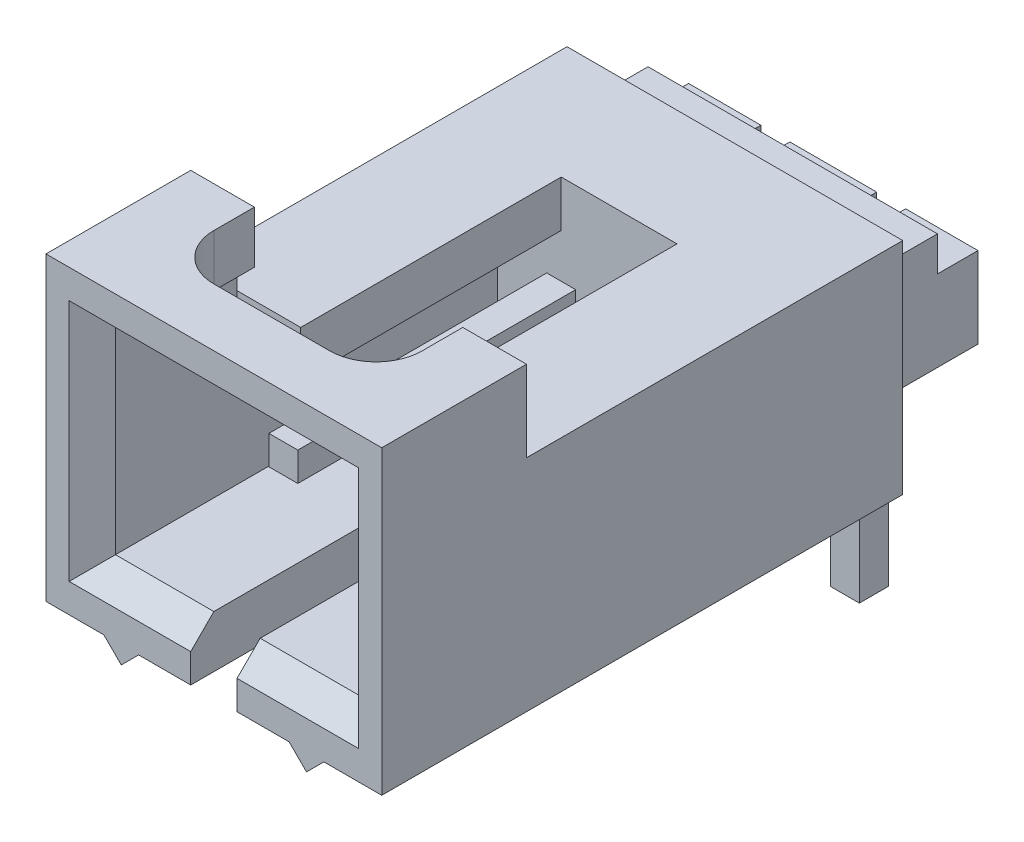
SolidWorks part; units mm, degrees
material "ABS"
ref_plane "Front Plane" through (0, 0, 0) normal (0, 0, 1) x (1, 0, 0)
ref_plane "Top Plane" through (0, 0, 0) normal (0, 1, 0) x (1, 0, 0)
ref_plane "Right Plane" through (0, 0, 0) normal (1, 0, 0) x (0, 0, -1)
ref_plane "Plane1" through (0, 0, 2.54) normal (0, 0, 1) x (1, 0, 0)
sketch "Sketch1" plane through (0, 0, 2.54) normal (0, 0, 1) x (1, 0, 0)
  line L0 (3.683, 2.286) -> (-3.683, 2.286)
  line L1 (-3.683, 2.286) -> (-3.683, -2.54)
  line L2 (-3.683, -2.54) -> (-2.413, -2.54)
  line L3 (-2.413, -2.54) -> (-1.651, -3.302)
  line L4 (-1.651, -3.302) -> (-1.651, -2.54)
  line L5 (-1.651, -2.54) -> (1.651, -2.54)
  line L6 (1.651, -2.54) -> (1.651, -3.302)
  line L7 (1.651, -3.302) -> (2.413, -2.54)
  line L8 (2.413, -2.54) -> (3.683, -2.54)
  line L9 (3.683, -2.54) -> (3.683, 2.286)
extrude "Boss-Extrude1" add sketch "Sketch1" against normal blind 8.255
sketch "Sketch2" plane through (0, 0, 2.54) normal (0, 0, 1) x (1, 0, 0)
  line L0 (2.667, -1.397) -> (2.667, 1.27)
  line L1 (2.667, 1.27) -> (1.27, 1.27)
  line L2 (1.27, 1.27) -> (1.27, 2.286)
  line L3 (1.27, 2.286) -> (-1.27, 2.286)
  line L4 (-1.27, 2.286) -> (-1.27, 1.27)
  line L5 (-1.27, 1.27) -> (-2.667, 1.27)
  line L6 (-2.667, 1.27) -> (-2.667, -1.397)
  line L7 (-2.667, -1.397) -> (-0.508, -1.397)
  line L8 (-0.508, -1.397) -> (-0.508, -2.54)
  line L9 (-0.508, -2.54) -> (0.508, -2.54)
  line L10 (0.508, -2.54) -> (0.508, -1.397)
  line L11 (0.508, -1.397) -> (2.667, -1.397)
extrude "Cut-Extrude1" cut sketch "Sketch2" against normal blind 5.715
sketch "Sketch3" plane through (0, 0, 2.54) normal (0, 0, 1) x (1, 0, 0)
  line L0 (0.508, -1.397) -> (2.667, -1.397)
  line L1 (2.667, -1.397) -> (2.667, 2.921)
  line L2 (2.667, 2.921) -> (-2.667, 2.921)
  line L3 (-2.667, 2.921) -> (-2.667, -1.397)
  line L4 (-2.667, -1.397) -> (-0.508, -1.397)
  line L5 (-0.508, -1.397) -> (-0.508, -2.54)
  line L6 (-0.508, -2.54) -> (-1.651, -2.54)
  line L7 (-1.651, -2.54) -> (-1.651, -3.302)
  line L8 (-1.651, -3.302) -> (-2.413, -2.54)
  line L9 (-2.413, -2.54) -> (-3.683, -2.54)
  line L10 (-3.683, -2.54) -> (-3.683, 4.064)
  line L11 (-3.683, 4.064) -> (3.683, 4.064)
  line L12 (3.683, 4.064) -> (3.683, -2.54)
  line L13 (3.683, -2.54) -> (2.413, -2.54)
  line L14 (2.413, -2.54) -> (1.651, -3.302)
  line L15 (1.651, -3.302) -> (1.651, -2.54)
  line L16 (1.651, -2.54) -> (0.508, -2.54)
  line L17 (0.508, -2.54) -> (0.508, -1.397)
extrude "Boss-Extrude2" add sketch "Sketch3" along normal blind 3.175
sketch "Sketch4" plane through (0, 0, 2.54) normal (0, 0, -1) x (-1, 0, 0)
  line L0 (2.286, 4.064) -> (-2.286, 4.064)
  line L1 (-2.286, 4.064) -> (-2.286, 2.921)
  line L2 (-2.286, 2.921) -> (2.286, 2.921)
  line L3 (2.286, 2.921) -> (2.286, 4.064)
extrude "Cut-Extrude2" cut sketch "Sketch4" against normal blind 1.905
sketch "Sketch5" plane through (0, 0, -3.175) normal (0, 0, 1) x (1, 0, 0)
  line L0 (-0.9525, -0.3302) -> (-1.5875, -0.3302)
  line L1 (-1.5875, -0.3302) -> (-1.5875, 0.3048)
  line L2 (-1.5875, 0.3048) -> (-0.9525, 0.3048)
  line L3 (-0.9525, 0.3048) -> (-0.9525, -0.3302)
extrude "Boss-Extrude3" add sketch "Sketch5" along normal blind 6.096
sketch "Sketch6" plane through (0, 0, -3.175) normal (0, 0, 1) x (1, 0, 0)
  line L0 (1.5875, -0.3302) -> (0.9525, -0.3302)
  line L1 (0.9525, -0.3302) -> (0.9525, 0.3048)
  line L2 (0.9525, 0.3048) -> (1.5875, 0.3048)
  line L3 (1.5875, 0.3048) -> (1.5875, -0.3302)
extrude "Boss-Extrude4" add sketch "Sketch6" along normal blind 6.096
sketch "Sketch7" plane through (0, 0, -5.715) normal (0, 0, -1) x (-1, 0, 0)
  line L0 (0.9525, -1.016) -> (0.9525, 0.0508)
  line L1 (0.9525, 0.0508) -> (1.5875, 0.0508)
  line L2 (1.5875, 0.0508) -> (1.5875, -1.016)
  line L3 (1.5875, -1.016) -> (0.9525, -1.016)
extrude "Boss-Extrude5" add sketch "Sketch7" along normal blind 1.778
sketch "Sketch8" plane through (0, 0, -5.715) normal (0, 0, -1) x (-1, 0, 0)
  line L0 (-1.5875, -1.016) -> (-1.5875, 0.0508)
  line L1 (-1.5875, 0.0508) -> (-0.9525, 0.0508)
  line L2 (-0.9525, 0.0508) -> (-0.9525, -1.016)
  line L3 (-0.9525, -1.016) -> (-1.5875, -1.016)
extrude "Boss-Extrude6" add sketch "Sketch8" along normal blind 1.778
sketch "Sketch9" plane through (0, -1.016, 0) normal (0, -1, 0) x (1, 0, 0)
  line L0 (-0.9525, -7.493) -> (-1.5875, -7.493)
  line L1 (-1.5875, -7.493) -> (-1.5875, -6.858)
  line L2 (-1.5875, -6.858) -> (-0.9525, -6.858)
  line L3 (-0.9525, -6.858) -> (-0.9525, -7.493)
extrude "Boss-Extrude7" add sketch "Sketch9" along normal blind 5.207
sketch "Sketch10" plane through (0, -1.016, 0) normal (0, -1, 0) x (1, 0, 0)
  line L0 (1.5875, -7.493) -> (0.9525, -7.493)
  line L1 (0.9525, -7.493) -> (0.9525, -6.858)
  line L2 (0.9525, -6.858) -> (1.5875, -6.858)
  line L3 (1.5875, -6.858) -> (1.5875, -7.493)
extrude "Boss-Extrude8" add sketch "Sketch10" along normal blind 5.207
ref_plane "Plane2" through (0, 0, -6.985) normal (0, 0, -1) x (-1, 0, 0)
sketch "Sketch11" plane through (0, 0, -6.985) normal (0, 0, -1) x (-1, 0, 0)
  line L0 (0.9525, 0.0508) -> (1.5875, 0.0508)
  line L1 (1.5875, 0.0508) -> (1.5875, -1.016)
  line L2 (1.5875, -1.016) -> (3.175, -1.016)
  line L3 (3.175, -1.016) -> (3.175, 1.524)
  line L4 (3.175, 1.524) -> (-3.175, 1.524)
  line L5 (-3.175, 1.524) -> (-3.175, -1.016)
  line L6 (-3.175, -1.016) -> (-1.5875, -1.016)
  line L7 (-1.5875, -1.016) -> (-1.5875, 0.0508)
  line L8 (-1.5875, 0.0508) -> (-0.9525, 0.0508)
  line L9 (-0.9525, 0.0508) -> (-0.9525, -1.016)
  line L10 (-0.9525, -1.016) -> (0.9525, -1.016)
  line L11 (0.9525, -1.016) -> (0.9525, 0.0508)
extrude "Boss-Extrude9" add sketch "Sketch11" against normal up to surface (1.27 mm away) up to face at (-1.27, -0.4826, -5.715)
ref_plane "Plane3" through (0, 0, -7.874) normal (0, 0, -1) x (-1, 0, 0)
sketch "Sketch12" plane through (0, 0, -7.874) normal (0, 0, -1) x (-1, 0, 0)
  line L0 (1.5875, -1.016) -> (3.175, -1.016)
  line L1 (3.175, -1.016) -> (3.175, 0.762)
  line L2 (3.175, 0.762) -> (1.5875, 0.762)
  line L3 (1.5875, 0.762) -> (1.5875, -1.016)
extrude "Boss-Extrude10" add sketch "Sketch12" against normal up to surface (0.889 mm away) up to face at (0, -0.2371, -6.985)
sketch "Sketch13" plane through (0, 0, -7.874) normal (0, 0, -1) x (-1, 0, 0)
  line L0 (-0.9525, -1.016) -> (0.9525, -1.016)
  line L1 (0.9525, -1.016) -> (0.9525, 0.762)
  line L2 (0.9525, 0.762) -> (-0.9525, 0.762)
  line L3 (-0.9525, 0.762) -> (-0.9525, -1.016)
extrude "Boss-Extrude11" add sketch "Sketch13" against normal up to surface (0.889 mm away) up to face at (0, 0.0593, -6.985)
sketch "Sketch14" plane through (0, 0, -7.874) normal (0, 0, -1) x (-1, 0, 0)
  line L0 (-3.175, -1.016) -> (-1.5875, -1.016)
  line L1 (-1.5875, -1.016) -> (-1.5875, 0.762)
  line L2 (-1.5875, 0.762) -> (-3.175, 0.762)
  line L3 (-3.175, 0.762) -> (-3.175, -1.016)
extrude "Boss-Extrude12" add sketch "Sketch14" against normal up to surface (0.889 mm away) up to face at (0, 0.3556, -6.985)
fillet "Fillet1" radius 1.27 1 edges at (1.27, 0.0508, -7.493) tangent propagation no
fillet "Fillet2" radius 1.27 1 edges at (-1.27, 0.0508, -7.493) tangent propagation no
chamfer "Chamfer1" distance 0.508 angle 45 1 edges at (1.9685, 1.27, 2.54)
chamfer "Chamfer2" distance 0.508 angle 45 1 edges at (-1.9685, 1.27, 2.54)
draft "Draft1" type of draft neutral plane draft angle 45 faces to draft 2 face at (1.651, -2.921, 0) face at (-1.651, -2.921, 0) neutral plane through (-1.651, -2.54, -5.715) neutral plane normal (0, -1, 0) parameters "D1"=45
chamfer "Chamfer3" distance 0.508 angle 45 5 edges at (1.5875, -1.397, 5.715) (2.667, 0.762, 5.715) (0, 2.921, 5.715) (-1.5875, -1.397, 5.715) (-2.667, 0.762, 5.715)
fillet "Fillet3" radius 1.016 2 edges at (2.286, 3.4925, 4.445) (-2.286, 3.4925, 4.445) tangent propagation no
ref_plane "Plane4" through (0, 0, -7.1755) normal (0, 0, -1) x (-1, 0, 0)
sketch "Sketch15" plane through (0, 0, -7.1755) normal (0, 0, -1) x (-1, 0, 0)
  line L0 (-0.9525, -6.223) -> (-1.5875, -6.223) construction
  line L1 (-0.9525, -6.223) -> (-1.5875, -6.223) construction
  line L2 (-1.27, -1006.223) -> (-1.27, 48993.777) construction
  point P5 (-1.27, -6.223)
